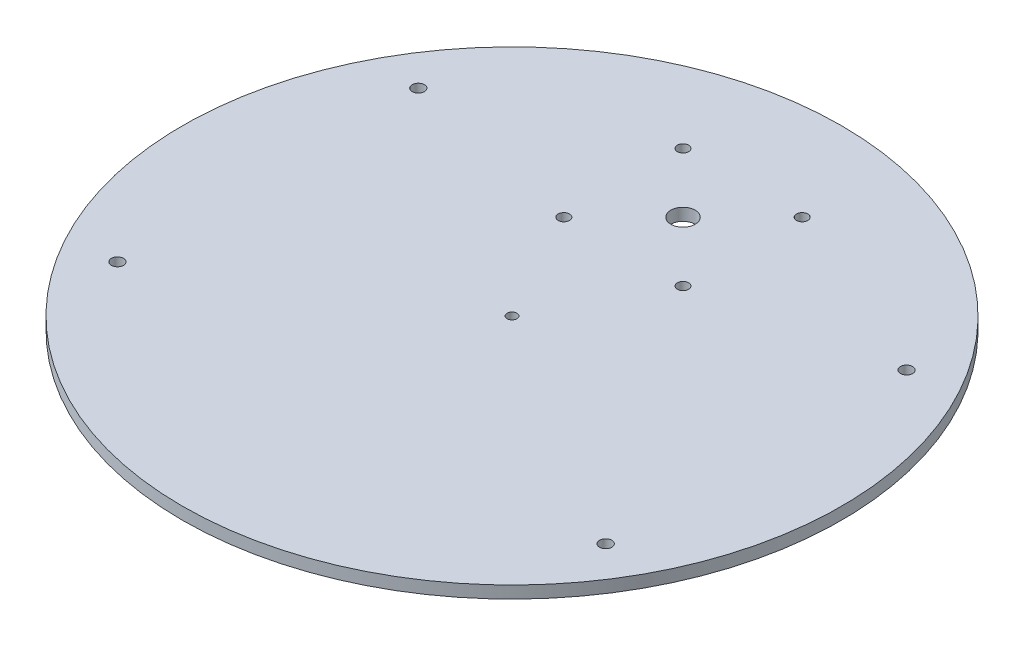
SolidWorks part; units mm, degrees
ref_plane "Front Plane" through (0, 0, 0) normal (0, 0, 1) x (1, 0, 0)
ref_plane "Top Plane" through (0, 0, 0) normal (0, 1, 0) x (1, 0, 0)
ref_plane "Right Plane" through (0, 0, 0) normal (1, 0, 0) x (0, 0, -1)
sketch "Sketch1" plane through (0, 0, 0) normal (0, 1, 0) x (1, 0, 0)
  circle A0 centre (0, 0) radius 85.725
  dimension "D1" = 171.45
extrude "Boss-Extrude1" add sketch "Sketch1" along normal blind 3.175
sketch "Sketch2" plane through (0, 3.175, 0) normal (0, 1, 0) x (1, 0, 0)
  line L0 (-63.5, 39.1325) -> (-63.5, -39.1325) construction
  line L1 (-63.5, -39.1325) -> (63.5, -39.1325) construction
  line L2 (63.5, -39.1325) -> (63.5, 39.1325) construction
  line L3 (63.5, 39.1325) -> (-63.5, 39.1325) construction
  circle A0 centre (-63.5, 39.1325) radius 1.5875
  circle A1 centre (63.5, 39.1325) radius 1.5875
  circle A2 centre (-63.5, -39.1325) radius 1.5875
  circle A3 centre (63.5, -39.1325) radius 1.5875
  dimension "D1" = 3.175
  dimension "D2" = 3.175
  dimension "D3" = 127
  dimension "D4" = 3.175
  dimension "D5" = 3.175
  dimension "D6" = 78.265
  dimension "D8" = 39.1325
  dimension "D9" = 63.5
extrude "Cut-Extrude1" cut sketch "Sketch2" against normal up to next
sketch "Sketch3" plane through (0, 3.175, 0) normal (0, 1, 0) x (1, 0, 0)
  line L0 (0, 44.4822) -> (0, 0) construction
  circle A0 centre (0, 44.4822) radius 3.175
  dimension "D1" = 6.35
  dimension "D2" = 44.4822
extrude "Cut-Extrude2" cut sketch "Sketch3" against normal up to next contours A0
ref_axis "Axis1" through (0, 3.175, 0) along (0, -1, 0)
sketch "Sketch5" plane through (0, 3.175, 0) normal (0, 1, 0) x (1, 0, 0)
  line L1 (-15.5004, 59.9825) -> (15.5003, 59.9825) construction
  line L2 (-15.5004, 59.9825) -> (-15.5003, 28.9818) construction
  line L3 (-15.5003, 28.9818) -> (15.5003, 28.9818) construction
  line L4 (15.5003, 59.9825) -> (15.5003, 28.9818) construction
  line L5 (-15.5004, 59.9825) -> (15.5003, 28.9818) construction
  line L6 (-15.5003, 28.9818) -> (15.5003, 59.9825) construction
  circle A0 centre (0, 44.4822) radius 3.175 construction
  circle A1 centre (0, 44.4822) radius 3.175 construction
  circle A2 centre (-15.5004, 59.9825) radius 1.4732
  circle A3 centre (15.5003, 59.9825) radius 1.4732
  circle A4 centre (-15.5003, 28.9818) radius 1.4732
  circle A5 centre (15.5003, 28.9818) radius 1.4732
  dimension "D3" = 2.9464
  dimension "D4" = 2.9464
  dimension "D5" = 2.9464
  dimension "D6" = 2.9464
  dimension "D1" = 31.0007
  dimension "D2" = 31.0007
extrude "Cut-Extrude3" cut sketch "Sketch5" against normal up to next
sketch "Sketch6" plane through (0, 3.175, 0) normal (0, 1, 0) x (1, 0, 0)
  circle A0 centre (0, 0) radius 1.27
  dimension "D1" = 2.54
extrude "center_hole" cut sketch "Sketch6" against normal up to next
